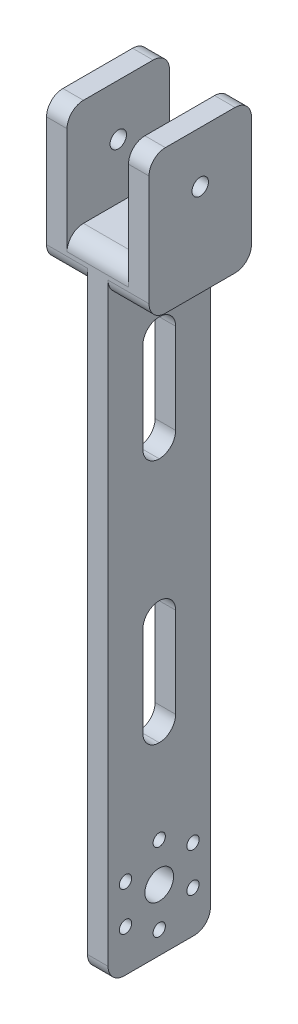
SolidWorks part; units mm, degrees
ref_plane "Ön Düzlem" through (0, 0, 0) normal (0, 0, 1) x (1, 0, 0)
ref_plane "Üst Düzlem" through (0, 0, 0) normal (0, 1, 0) x (1, 0, 0)
ref_plane "Sağ Düzlem" through (0, 0, 0) normal (1, 0, 0) x (0, 0, -1)
sketch "Çizim1" plane through (0, 0, 0) normal (0, 0, 1) x (1, 0, 0)
  line L0 (-2.5, 72.5) -> (-12.5, 72.5)
  line L1 (2.5, -72.5) -> (-2.5, -72.5)
  line L2 (2.5, -72.5) -> (2.5, 72.5)
  line L4 (-2.5, -72.5) -> (-2.5, 72.5)
  line L5 (2.5, -72.5) -> (-2.5, 72.5) construction
  line L6 (2.5, 72.5) -> (-2.5, -72.5) construction
  line L7 (-12.5, 72.5) -> (-12.5, 107.5)
  line L8 (-12.5, 107.5) -> (-7.5, 107.5)
  line L9 (-7.5, 107.5) -> (-7.5, 81.5)
  line L10 (-7.5, 81.5) -> (7.5, 81.5)
  line L11 (7.5, 81.5) -> (7.5, 107.5)
  line L12 (7.5, 107.5) -> (12.5, 107.5)
  line L13 (12.5, 107.5) -> (12.5, 72.5)
  line L14 (12.5, 72.5) -> (2.5, 72.5)
  point P0 (0, 0)
  dimension "D1" = 145
  dimension "D2" = 5
  dimension "D3" = 10
  dimension "D4" = 35
  dimension "D5" = 5
  dimension "D6" = 26
  dimension "D7" = 15
  dimension "D8" = 35
  dimension "D9" = 5
  dimension "D10" = 145
extrude "Yükseklik-Ekstrüzyon1" add sketch "Çizim1" along normal blind 25
sketch "Çizim2" plane through (-12.5, 0, 0) normal (-1, 0, 0) x (0, 0, 1)
  line L0 (0, 107.5) -> (0, 72.5) construction
  line L2 (25, 107.5) -> (0, 107.5) construction
  circle A0 centre (12.5, 95) radius 2
  dimension "D3" = 4
  dimension "D1" = 12.5
  dimension "D2" = 12.5
extrude "Kes-Ekstrüzyon1" cut sketch "Çizim2" against normal blind 25
sketch "Çizim3" plane through (-2.5, 0, 0) normal (-1, 0, 0) x (0, 0, 1)
  line L0 (25, 72.5) -> (25, -72.5) construction
  line L1 (8.5, 62.5) -> (16.5, 62.5)
  line L2 (8.5, 62.5) -> (8.5, 32.5)
  line L3 (8.5, 32.5) -> (16.5, 32.5)
  line L4 (16.5, 62.5) -> (16.5, 32.5)
  line L5 (8.5, 2.5) -> (16.5, 2.5)
  line L6 (8.5, 2.5) -> (8.5, -27.5)
  line L7 (8.5, -27.5) -> (16.5, -27.5)
  line L8 (16.5, 2.5) -> (16.5, -27.5)
  line L9 (25, -72.5) -> (0, -72.5) construction
  line L10 (0, 72.5) -> (0, -72.5) construction
  line L11 (25, 107.5) -> (0, 107.5) construction
  circle A0 centre (12.5, -57.5) radius 3.5
  dimension "D1" = 7
  dimension "D2" = 12.5
  dimension "D3" = 15
  dimension "D4" = 8.5
  dimension "D5" = 8.5
  dimension "D6" = 45
  dimension "D7" = 45
  dimension "D8" = 30
  dimension "D9" = 30
  dimension "D10" = 8.5
  dimension "D11" = 8.5
extrude "Kes-Ekstrüzyon2" cut sketch "Çizim3" against normal blind 10
sketch "Çizim4" plane through (-2.5, 0, 0) normal (-1, 0, 0) x (0, 0, 1)
  line L0 (25, 72.5) -> (25, -72.5) construction
  circle A0 centre (12.5, -48) radius 1.5
  dimension "D3" = 3
  dimension "D1" = 12.5
  dimension "D2" = 9.5
extrude "Kes-Ekstrüzyon3" cut sketch "Çizim4" against normal blind 10
pattern_circular "Dairesel Kaplama2" count 6 over 360 about axis through (7.5, -57.5, 12.5) along (-1, 0, 0) of "Kes-Ekstrüzyon3"
fillet "Radyus1" radius 4 20 edges at (0, 81.5, 25) (0, 81.5, 0) (-10, 107.5, 25) (10, 107.5, 25) (10, 107.5, 0) (-10, 107.5, 0) (7.5, 72.5, 0) (7.5, 72.5, 25) (-7.5, 72.5, 25) (-7.5, 72.5, 0) (0, 32.5, 16.5) (0, 62.5, 16.5) (0, 32.5, 8.5) (0, 62.5, 8.5) (0, -27.5, 16.5) (0, -27.5, 8.5) (0, 2.5, 16.5) (0, 2.5, 8.5) (0, -72.5, 25) (0, -72.5, 0)
